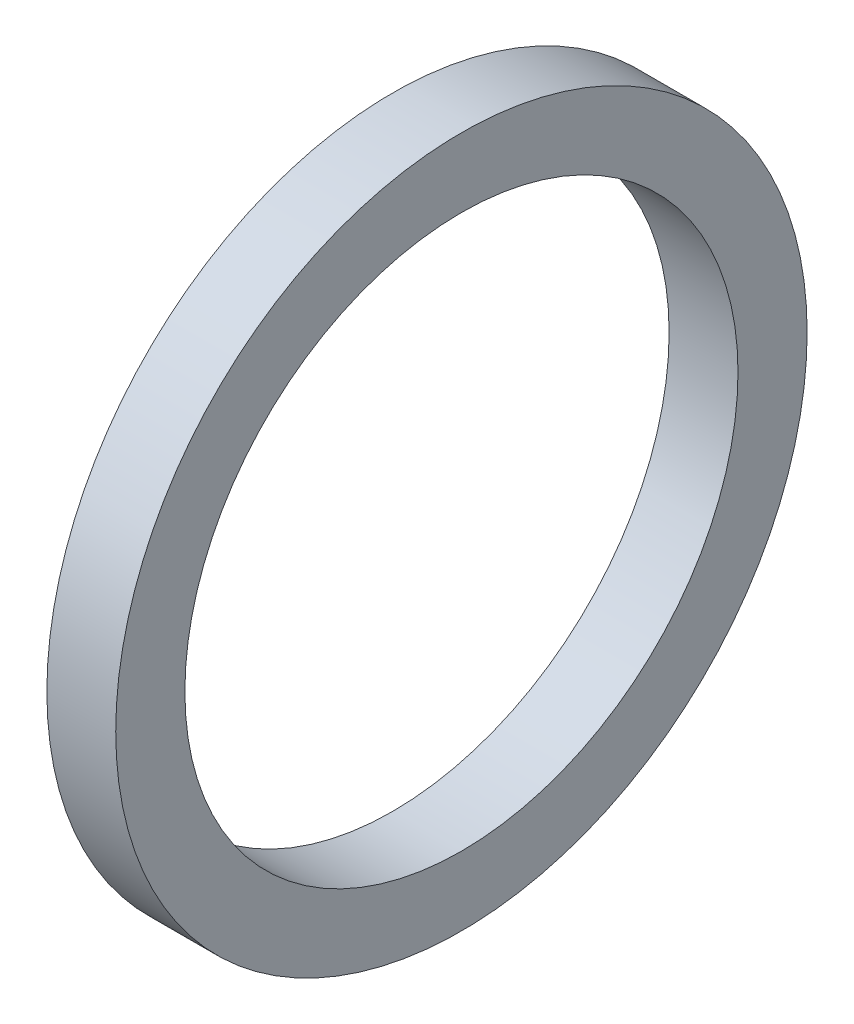
SolidWorks part; units mm, degrees
ref_plane "Front Plane" through (0, 0, 0) normal (0, 0, 1) x (1, 0, 0)
ref_plane "Top Plane" through (0, 0, 0) normal (0, 1, 0) x (1, 0, 0)
ref_plane "Right Plane" through (0, 0, 0) normal (1, 0, 0) x (0, 0, -1)
sketch "Sketch2" plane through (0, 0, 0) normal (0, 0, 1) x (1, 0, 0)
  line L0 (0, 0) -> (58.591, 0) construction
  line L2 (0, 0) -> (18.4, 0)
  line L3 (0, 0) -> (0, 2.5)
  line L4 (0, 2.5) -> (18.4, 2.5)
  line L5 (18.4, 0) -> (18.4, 2.5)
  line L6 (6.0094, 2.5) -> (6.0094, 6)
  line L11 (6.0094, 6) -> (9.9794, 6)
  line L16 (12.9794, 6) -> (12.9794, 3)
  line L17 (12.9794, 3) -> (13.6398, 3)
  line L18 (13.6398, 3) -> (13.6398, 2.5)
  line L19 (13.6398, 2.5) -> (6.0094, 2.5)
  line L22 (13.6398, 2.5) -> (16.1198, 2.5)
  line L23 (13.6398, 2.5) -> (13.6398, 4)
  line L24 (13.6398, 4) -> (16.1198, 4)
  line L25 (16.1198, 2.5) -> (16.1198, 4)
  line L27 (6.0094, 6) -> (9.9794, 6)
  line L28 (6.0094, 6) -> (6.0094, 9)
  line L29 (6.0094, 9) -> (9.9794, 9)
  line L30 (9.9794, 6) -> (9.9794, 9)
  line L31 (6.0094, 9) -> (6.0094, 8.25)
  line L32 (6.0094, 8.25) -> (5.0094, 8.25)
  line L33 (8.6609, 22.001) -> (8.6609, 12.476) construction
  line L34 (5.0094, 12.476) -> (12.3124, 12.476)
  line L35 (9.9794, 9) -> (12.3124, 9)
  line L36 (5.0094, 7.9375) -> (1.8344, 7.9375)
  line L37 (5.0094, 8.25) -> (5.0094, 12.476)
  line L38 (5.0094, 7.9375) -> (5.0094, 13.9365)
  line L39 (5.0094, 13.9365) -> (1.8344, 13.9365)
  line L40 (1.8344, 7.9375) -> (1.8344, 13.9365)
  line L41 (5.0094, 22.001) -> (12.3124, 22.001)
  line L42 (5.0094, 22.001) -> (5.0094, 30.1625)
  line L43 (5.0094, 30.1625) -> (12.3124, 30.1625)
  line L44 (12.3124, 22.001) -> (12.3124, 30.1625)
  line L49 (16.6398, 22.001) -> (16.6398, 7.5)
  line L51 (23.0198, 7.5) -> (23.0198, 6.5)
  line L54 (16.1198, 4) -> (13.6398, 4)
  line L56 (18.0398, 7.5) -> (23.0198, 7.5)
  line L57 (13.3124, 22.001) -> (16.6398, 22.001)
  line L58 (16.1198, 3.5) -> (20.0198, 3.5)
  line L59 (29.9098, 14) -> (26.9098, 11)
  line L60 (4.0094, 31.75) -> (18.0398, 31.75)
  line L61 (18.0398, 7.5) -> (23.0198, 7.5)
  line L62 (18.0398, 7.5) -> (18.0398, 12)
  line L63 (18.0398, 12) -> (23.0198, 12)
  line L64 (23.0198, 7.5) -> (23.0198, 12)
  line L65 (18.0398, 31.75) -> (18.0398, 12)
  line L66 (23.0198, 11) -> (26.9098, 11)
  line L67 (34.8098, 23) -> (31.3098, 19.5)
  line L68 (35.8098, 31) -> (38.7998, 33.99)
  line L69 (29.9098, 14) -> (29.9098, 15)
  line L70 (29.9098, 15) -> (22.9398, 15)
  line L71 (22.9398, 15) -> (21.0398, 15)
  line L72 (18.0398, 7.5) -> (16.6398, 7.5)
  line L73 (21.0398, 15) -> (21.0398, 43)
  line L74 (19.5798, 40) -> (9.6198, 40)
  line L75 (9.6198, 40) -> (4.0094, 40)
  line L76 (21.0398, 43) -> (19.5798, 43)
  line L77 (22.9398, 15) -> (29.9098, 15)
  line L78 (22.9398, 15) -> (22.9398, 21)
  line L79 (22.9398, 21) -> (29.9098, 21)
  line L80 (29.9098, 15) -> (29.9098, 21)
  line L81 (9.6198, 40) -> (19.5798, 40)
  line L82 (9.6198, 40) -> (9.6198, 50)
  line L83 (9.6198, 50) -> (19.5798, 50)
  line L84 (19.5798, 40) -> (19.5798, 50)
  line L85 (4.0094, 40) -> (4.0094, 31.75)
  line L86 (12.9794, 3) -> (12.9794, 2.5)
  line L87 (31.3098, 19.5) -> (29.9098, 19.5)
  line L88 (21.4694, 63.5) -> (21.4694, 51.308)
  line L89 (21.4694, 63.5) -> (25.9398, 63.5)
  line L90 (25.9398, 63.5) -> (25.9398, 25)
  line L91 (27.8398, 25) -> (25.9398, 25)
  line L92 (9.6198, 48) -> (8.1598, 48)
  line L93 (8.1598, 48) -> (8.1598, 53.476)
  line L94 (8.1598, 53.476) -> (19.5798, 53.476)
  line L95 (19.5798, 53.476) -> (19.5798, 50)
  line L96 (13.8698, 63.001) -> (13.8698, 53.476) construction
  line L97 (8.1598, 63.001) -> (19.5798, 63.001)
  line L98 (8.1598, 63.001) -> (8.1598, 68.2625)
  line L99 (8.1598, 68.2625) -> (19.5798, 68.2625)
  line L100 (19.5798, 63.001) -> (19.5798, 68.2625)
  line L101 (12.9794, 6) -> (11.9794, 6)
  line L102 (8.1598, 44.825) -> (4.9848, 44.825)
  line L103 (8.1598, 44.825) -> (8.1598, 54.9365)
  line L104 (8.1598, 54.9365) -> (4.9848, 54.9365)
  line L106 (9.9794, 6) -> (10.8794, 6)
  line L107 (27.8398, 25) -> (34.8098, 25)
  line L108 (34.8098, 25) -> (34.8098, 23)
  line L109 (0, 0) -> (-2, 0)
  line L110 (0, 0) -> (0, 11)
  line L111 (27.8398, 25) -> (34.8098, 25)
  line L112 (27.8398, 25) -> (27.8398, 32.5)
  line L113 (27.8398, 32.5) -> (34.8098, 32.5)
  line L114 (34.8098, 25) -> (34.8098, 32.5)
  line L115 (35.8098, 31) -> (34.8098, 31)
  line L116 (27.8398, 32.5) -> (27.8398, 64.5)
  line L117 (20.5373, 74.025) -> (6.2023, 74.025)
  line L118 (6.2023, 74.025) -> (6.2023, 76.2)
  line L119 (38.7998, 47.29) -> (30.8398, 55.25)
  line L120 (0, 11) -> (-2, 11)
  line L121 (38.7998, 43.815) -> (30.8623, 43.815)
  line L123 (-4.8152, 69.85) -> (1.5348, 76.2)
  line L124 (38.7998, 47.29) -> (38.7998, 33.99)
  line L125 (-2, 0) -> (-2, 11)
  line L126 (38.7998, 37.465) -> (30.8623, 37.465)
  line L127 (30.8623, 43.815) -> (30.8623, 37.465)
  line L128 (6.0094, 2.5) -> (6.0094, 0)
  line L129 (-0.0152, 63.5) -> (-0.0152, 30)
  line L132 (4.9848, 63.5) -> (-0.0152, 63.5)
  line L136 (-1.8152, 30) -> (-11.7752, 30)
  line L138 (-13.7752, 25.4) -> (-2, 25.4)
  line L139 (-2, 25.4) -> (-2, 11.5)
  line L140 (27.8398, 64.5) -> (20.5373, 64.5)
  line L141 (-1.8152, 30) -> (-11.7752, 30)
  line L142 (-1.8152, 30) -> (-1.8152, 39)
  line L143 (-1.8152, 39) -> (-11.7752, 39)
  line L144 (-11.7752, 30) -> (-11.7752, 39)
  line L145 (20.5373, 64.5) -> (20.5373, 74.025)
  line L146 (-12.7752, 37) -> (-12.7752, 47.29)
  line L147 (-12.7752, 37) -> (-11.7752, 37)
  line L148 (30.8398, 55.25) -> (30.8398, 76.2)
  line L149 (11.9794, 6) -> (11.9794, 5.45)
  line L154 (-2, 11.5) -> (0.5, 11.5)
  line L155 (4.9848, 60.6197) -> (24.0348, 60.6197)
  line L160 (4.9848, 60.6197) -> (4.9848, 55.8572)
  line L161 (4.9848, 55.8572) -> (24.0348, 55.8572)
  line L166 (24.0348, 60.6197) -> (24.0348, 55.8572)
  line L167 (4.9848, 60.6197) -> (24.0348, 55.8572) construction
  line L172 (4.9848, 55.8572) -> (24.0348, 60.6197) construction
  line L173 (24.0348, 62.2072) -> (25.9398, 62.2072)
  line L174 (11.9794, 5.45) -> (10.8794, 5.45)
  line L175 (10.8794, 6) -> (10.8794, 5.45)
  line L176 (24.0348, 62.2072) -> (24.0348, 54.2697)
  line L177 (24.0348, 54.2697) -> (25.9398, 54.2697)
  line L178 (25.9398, 62.2072) -> (25.9398, 54.2697)
  line L179 (24.0348, 62.2072) -> (25.9398, 54.2697) construction
  line L180 (24.0348, 54.2697) -> (25.9398, 62.2072) construction
  line L181 (3, 19.6197) -> (15.7, 19.6197)
  line L182 (3, 19.6197) -> (3, 14.8572)
  line L183 (3, 14.8572) -> (15.7, 14.8572)
  line L184 (15.7, 19.6197) -> (15.7, 14.8572)
  line L185 (3, 19.6197) -> (15.7, 14.8572) construction
  line L186 (3, 14.8572) -> (15.7, 19.6197) construction
  line L187 (15.7, 21.2072) -> (16.6398, 21.2072)
  line L188 (15.7, 21.2072) -> (15.7, 13.2697)
  line L189 (15.7, 13.2697) -> (16.6398, 13.2697)
  line L190 (16.6398, 21.2072) -> (16.6398, 13.2697)
  line L191 (15.7, 21.2072) -> (16.6398, 13.2697) construction
  line L192 (15.7, 13.2697) -> (16.6398, 21.2072) construction
  line L193 (0.5, 11.5) -> (0.5, 6.9375)
  line L194 (0.5, 6.9375) -> (1.8344, 6.9375)
  line L195 (23.0198, 6.5) -> (20.0198, 3.5)
  line L196 (4.9848, 63.5) -> (4.9848, 54.9365)
  line L197 (3, 43.825) -> (4.9848, 43.825)
  line L198 (1.8344, 6.9375) -> (1.8344, 7.9375)
  line L199 (6.0094, 0) -> (12.9794, 0)
  line L200 (12.9794, 0) -> (12.9794, 2.5)
  line L201 (18.0398, 31.75) -> (18.0398, 35.875)
  line L202 (18.0398, 35.875) -> (21.0398, 35.875)
  line L203 (30.8398, 76.2) -> (6.2023, 76.2)
  line L204 (2.7573, 69.85) -> (7.2023, 69.85) construction
  line L205 (7.2023, 67.4688) -> (26.2523, 67.4688)
  line L206 (7.2023, 74.025) -> (7.2023, 64.5)
  line L207 (7.2023, 64.5) -> (-1.8152, 64.5)
  line L208 (-1.8152, 64.5) -> (-1.8152, 39)
  line L209 (-12.7752, 47.29) -> (-4.8152, 55.25)
  line L210 (-4.8152, 55.25) -> (-4.8152, 69.85)
  line L211 (7.2023, 67.4688) -> (7.2023, 72.2312)
  line L212 (7.2023, 72.2312) -> (26.2523, 72.2313)
  line L213 (26.2523, 67.4688) -> (26.2523, 72.2313)
  line L214 (26.2523, 73.8187) -> (30.8398, 73.8187)
  line L215 (26.2523, 73.8187) -> (26.2523, 65.8813)
  line L216 (26.2523, 65.8813) -> (30.8398, 65.8813)
  line L217 (30.8398, 73.8187) -> (30.8398, 65.8813)
  line L218 (2.7573, 72.2313) -> (24.9823, 72.2313)
  line L219 (2.7573, 72.2313) -> (2.7573, 67.4687)
  line L220 (2.7573, 67.4687) -> (24.9823, 67.4687)
  line L221 (24.9823, 72.2313) -> (24.9823, 67.4687)
  line L222 (24.9823, 69.85) -> (20.5373, 69.85) construction
  line L223 (21.4694, 51.308) -> (22.9398, 51.308)
  line L224 (22.9398, 51.308) -> (22.9398, 21)
  line L225 (13.6398, 4) -> (13.6398, 12.2697)
  line L226 (13.6398, 12.2697) -> (13.3124, 12.2697)
  line L227 (13.3124, 12.2697) -> (13.3124, 22.001)
  line L228 (12.3124, 9) -> (12.3124, 12.476)
  line L229 (-1.8152, 30) -> (-0.0152, 30)
  line L230 (8.1598, 65.6317) -> (2.7573, 65.6317) construction
  line L231 (19.5798, 65.6317) -> (24.9823, 65.6317) construction
  line L232 (1.5348, 76.2) -> (6.2023, 76.2)
  line L233 (-11.7752, 30) -> (-13.7752, 30)
  line L234 (-13.7752, 30) -> (-13.7752, 25.4)
  line L235 (3, 13.9365) -> (3, 43.825)
  line L236 (4.9848, 54.9365) -> (4.9848, 44.825)
  line L237 (4.9848, 43.825) -> (4.9848, 44.825)
  circle A0 centre (26.8898, 25.95) radius 0.95
  circle A1 centre (21.9898, 15.95) radius 0.95
  circle A2 centre (17.3398, 8.2) radius 0.7
  circle A3 centre (10.4294, 6.45) radius 0.45
  circle A4 centre (-0.9152, 30.9) radius 0.9
  point P7 (24.9873, 58.2385)
  point P131 (16.1699, 17.2385)
  point P135 (14.5098, 58.2385)
  point P146 (9.35, 17.2385)
sketch "Sketch3" plane through (0, 0, 0) normal (0, 0, 1) x (1, 0, 0)
  line L0 (19.5798, 40) -> (9.6198, 40) construction
  line L1 (9.6198, 40) -> (9.6198, 50) construction
  line L2 (9.6198, 50) -> (19.5798, 50) construction
  line L3 (19.5798, 40) -> (19.5798, 50) construction
  line L4 (19.5798, 40) -> (9.6198, 40)
  line L5 (9.6198, 40) -> (9.6198, 50)
  line L6 (9.6198, 50) -> (19.5798, 50)
  line L7 (19.5798, 40) -> (19.5798, 50)
revolve "Revolve1" add sketch "Sketch3" angle 360 about L0
